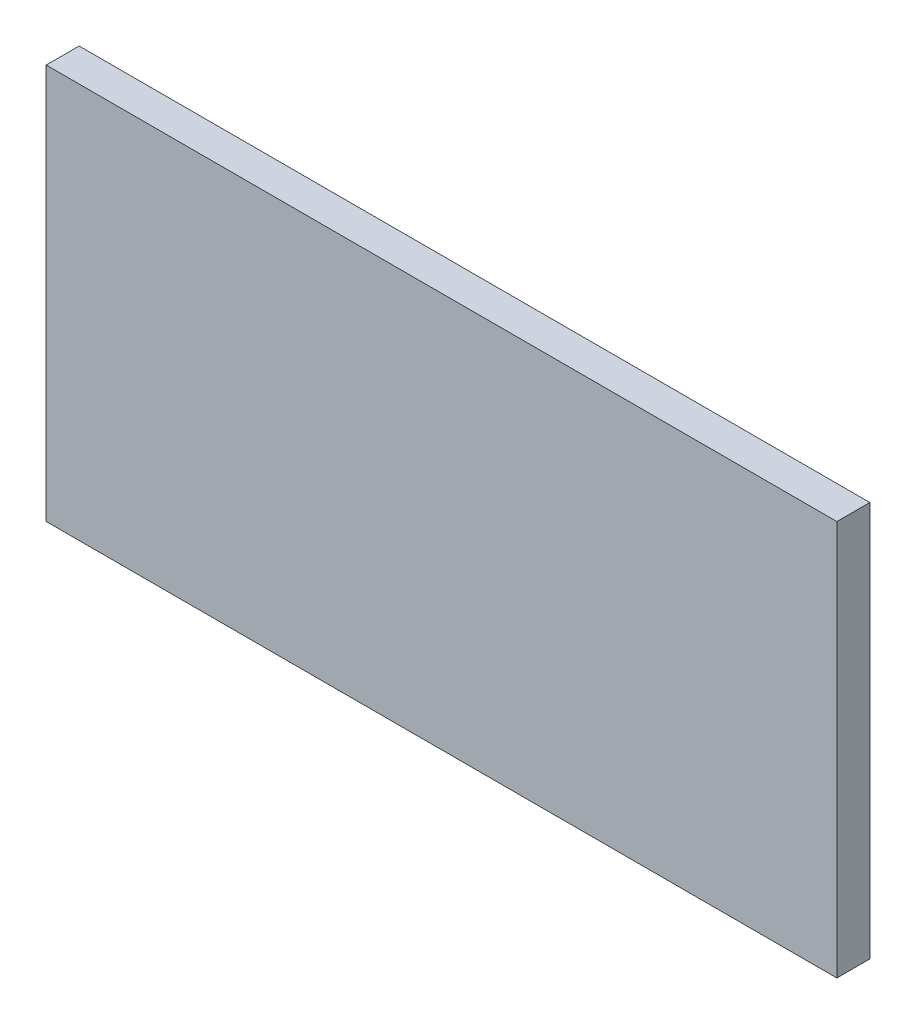
SolidWorks part; units mm, degrees
ref_plane "前视基准面" through (0, 0, 0) normal (0, 0, 1) x (1, 0, 0)
ref_plane "上视基准面" through (0, 0, 0) normal (0, 1, 0) x (1, 0, 0)
ref_plane "右视基准面" through (0, 0, 0) normal (1, 0, 0) x (0, 0, -1)
other "Configuration Table"
sketch "Sketch1" plane through (0, 0, 0) normal (0, 0, 1) x (1, 0, 0)
  line L1 (-600, -300) -> (600, -300)
  line L2 (-600, -300) -> (-600, 300)
  line L3 (-600, 300) -> (600, 300)
  line L4 (600, -300) -> (600, 300)
  line L5 (-600, -300) -> (600, 300) construction
  line L6 (-600, 300) -> (600, -300) construction
  point P0 (0, 0)
extrude "Boss-Extrude1" add sketch "Sketch1" along normal blind 25 and the other way blind 25
ref_plane "face_bottom" through (0, 0, -12.5) normal (0, 0, 1) x (1, 0, 0)
ref_plane "face_top" through (0, 0, 12.5) normal (0, 0, 1) x (1, 0, 0)
sketch3d "3DSketch1"
  line L0 (550, 250, -12.5) -> (550, 250, -11.5) construction
ref_axis "corner_fl_xp_yp" through (550, 250, -12.5) along (0, 0, 1)
sketch3d "3DSketch2"
  line L0 (550, -250, -12.5) -> (550, -250, -11.5) construction
ref_axis "corner_fl_xp_ym" through (550, -250, -12.5) along (0, 0, 1)
sketch3d "3DSketch3"
  line L0 (-550, 250, -12.5) -> (-550, 250, -11.5) construction
ref_axis "corner_fl_xm_yp" through (-550, 250, -12.5) along (0, 0, 1)
sketch3d "3DSketch4"
  line L0 (-550, -250, -12.5) -> (-550, -250, -11.5) construction
ref_axis "corner_fl_xm_ym" through (-550, -250, -12.5) along (0, 0, 1)
